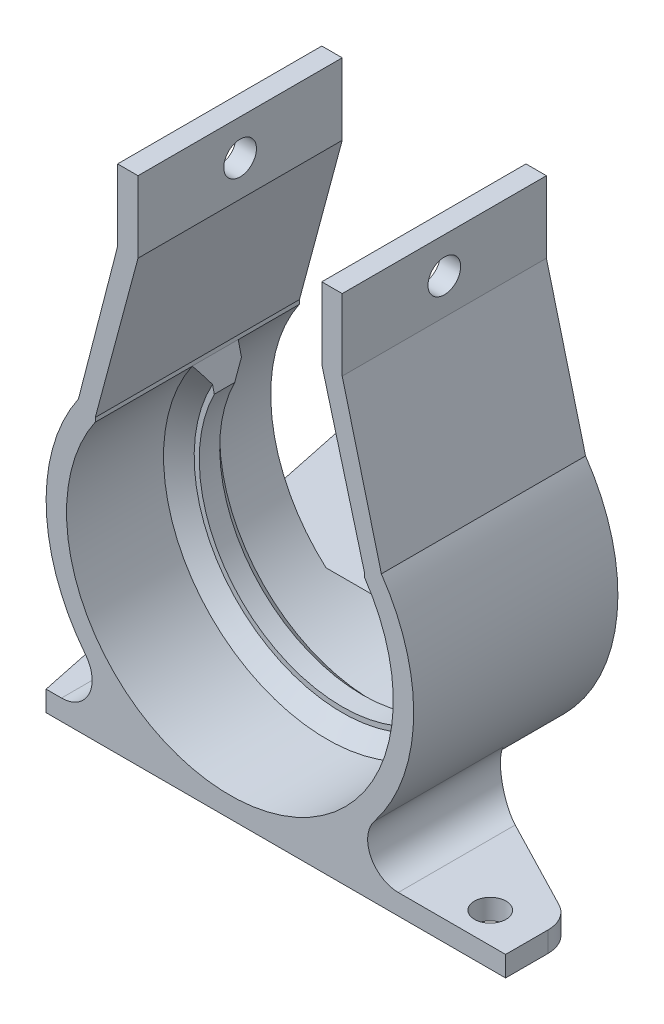
SolidWorks part; units mm, degrees
ref_plane "Front" through (0, 0, 0) normal (0, 0, 1) x (1, 0, 0)
ref_plane "Top" through (0, 0, 0) normal (0, 1, 0) x (1, 0, 0)
ref_plane "Right" through (0, 0, 0) normal (1, 0, 0) x (0, 0, -1)
sketch "Эскиз1" plane through (0, 0, 0) normal (0, 0, 1) x (1, 0, 0)
  circle A0 centre (0, 0) radius 16
  circle A1 centre (0, 0) radius 18
extrude "Бобышка-Вытянуть2" add sketch "Эскиз1" along normal blind 6
sketch "Эскиз2" plane through (0, 0, 6) normal (0, 0, 1) x (1, 0, 0)
  circle A0 centre (0, 0) radius 14
  circle A1 centre (0, 0) radius 18 construction
  circle A2 centre (0, 0) radius 18
extrude "Бобышка-Вытянуть3" add sketch "Эскиз2" along normal blind 3
sketch "Эскиз3" plane through (0, 0, 0) normal (0, 0, -1) x (-1, 0, 0)
  circle A0 centre (0, 0) radius 16 construction
  circle A1 centre (0, 0) radius 18 construction
  circle A2 centre (0, 0) radius 16
  circle A3 centre (0, 0) radius 18
extrude "Бобышка-Вытянуть5" add sketch "Эскиз3" against normal blind 20
sketch "Эскиз4" plane through (0, 0, 20) normal (0, 0, 1) x (1, 0, 0)
  line L0 (0, 0) -> (-14.8349, 10.1945)
  line L1 (14.8349, 10.1945) -> (0, 0)
  circle A0 centre (0, 0) radius 18 construction
  arc A1 (14.8349, 10.1945) -> (-14.8349, 10.1945) centre (0, 0) ccw
extrude "Вырез-Вытянуть1" cut sketch "Эскиз4" against normal blind 20
sketch "Эскиз6" plane through (0, 0, 9) normal (0, 0, 1) x (1, 0, 0)
  line L0 (-13.1865, 9.0617) -> (-12.5248, 6.2553)
  line L1 (12.5248, 6.2553) -> (13.1865, 9.0617)
  line L2 (13.1865, 9.0617) -> (-13.1865, 9.0617)
  line L3 (-12.5248, 6.2553) -> (12.5248, 6.2553)
  arc A0 (-11.5382, 7.929) -> (11.5382, 7.929) centre (0, 0) ccw construction
extrude "Вырез-Вытянуть2" cut sketch "Эскиз6" against normal blind 20
ref_plane "Плоскость1" through (0, 9.05, 0) normal (0, 1, 0) x (1, 0, 0)
sketch "Эскиз8" plane through (0, 9.05, 0) normal (0, 1, 0) x (1, 0, 0)
  line L0 (-13.1865, -20) -> (-13.1865, -9) construction
  line L1 (-13.1865, -9) -> (-13.1865, -6) construction
  line L2 (-13.1865, -6) -> (-13.1865, 0) construction
  line L3 (-13.1865, 0) -> (-14.8349, 0) construction
  line L4 (-14.8349, 0) -> (-14.8349, -20) construction
  line L5 (-14.8349, -20) -> (-13.1865, -20) construction
  line L6 (13.1865, 0) -> (13.1865, -6) construction
  line L7 (13.1865, -6) -> (13.1865, -9) construction
  line L8 (13.1865, -9) -> (13.1865, -20) construction
  line L9 (13.1865, -20) -> (14.8349, -20) construction
  line L10 (14.8349, -20) -> (14.8349, 0) construction
  line L11 (14.8349, 0) -> (13.1865, 0) construction
  line L12 (-13.1865, -20) -> (-13.1865, -9)
  line L13 (-13.1865, -9) -> (-13.1865, -6)
  line L14 (-13.1865, -6) -> (-13.1865, 0)
  line L15 (-13.1865, 0) -> (-14.8349, 0)
  line L16 (-14.8349, 0) -> (-14.8349, -20)
  line L17 (-14.8349, -20) -> (-13.1865, -20)
  line L18 (13.1865, 0) -> (13.1865, -6)
  line L19 (13.1865, -6) -> (13.1865, -9)
  line L20 (13.1865, -9) -> (13.1865, -20)
  line L21 (13.1865, -20) -> (14.8349, -20)
  line L22 (14.8349, -20) -> (14.8349, 0)
  line L23 (14.8349, 0) -> (13.1865, 0)
extrude "Бобышка-Вытянуть8" add sketch "Эскиз8" along normal blind 23
sketch "Эскиз10" plane through (0, 0, 20) normal (0, 0, 1) x (1, 0, 0)
  line L0 (-13.1865, 32.05) -> (13.1865, 32.05) construction
  line L1 (0, 32.05) -> (0, 0) construction
  line L2 (0, 32.05) -> (-11, 32.05) construction
  line L3 (0, 32.05) -> (11, 32.05) construction
  line L4 (-11, 32.05) -> (-11, 25.05)
  line L5 (-11, 32.05) -> (-9, 32.05)
  line L6 (-9, 32.05) -> (-9, 25.05)
  line L7 (-11, 25.05) -> (-14.8349, 10.1945)
  line L8 (-14.8349, 32.05) -> (-14.8349, 10.1945) construction
  line L9 (-9, 25.05) -> (-13.1865, 9.4503)
  line L10 (-13.1865, 32.05) -> (-13.1865, 9.05) construction
  line L11 (-13.1865, 9.4503) -> (-14.8349, 10.1945)
  line L12 (13.1865, 9.4503) -> (14.8349, 10.1945)
  line L13 (11, 25.05) -> (14.8349, 10.1945)
  line L14 (9, 25.05) -> (13.1865, 9.4503)
  line L15 (9, 32.05) -> (9, 25.05)
  line L16 (11, 32.05) -> (9, 32.05)
  line L17 (11, 32.05) -> (11, 25.05)
extrude "Бобышка-Вытянуть9" add sketch "Эскиз10" against normal blind 21
sketch "Эскиз11" plane through (0, 0, 0) normal (0, 0, -1) x (-1, 0, 0)
  line L0 (13.1865, 32.05) -> (13.1865, 16.5797) construction
  line L1 (13.1865, 16.5797) -> (14.8349, 10.1945) construction
  line L2 (14.8349, 10.1945) -> (14.8349, 32.05) construction
  line L3 (14.8349, 32.05) -> (13.1865, 32.05) construction
  line L4 (-14.8349, 32.05) -> (-14.8349, 10.1945) construction
  line L5 (-14.8349, 10.1945) -> (-13.1865, 16.5797) construction
  line L6 (-13.1865, 16.5797) -> (-13.1865, 32.05) construction
  line L7 (-13.1865, 32.05) -> (-14.8349, 32.05) construction
  line L8 (13.1865, 32.05) -> (13.1865, 16.5797)
  line L9 (13.1865, 16.5797) -> (14.8349, 10.1945)
  line L10 (14.8349, 10.1945) -> (14.8349, 32.05)
  line L11 (14.8349, 32.05) -> (13.1865, 32.05)
  line L12 (-14.8349, 32.05) -> (-14.8349, 10.1945)
  line L13 (-14.8349, 10.1945) -> (-13.1865, 16.5797)
  line L14 (-13.1865, 16.5797) -> (-13.1865, 32.05)
  line L15 (-13.1865, 32.05) -> (-14.8349, 32.05)
extrude "Вырез-Вытянуть3" cut sketch "Эскиз11" against normal blind 21
sketch "Эскиз12" plane through (-11, 0, 0) normal (-1, 0, 0) x (0, 0, 1)
  line L0 (0, 10.1945) -> (0, 32.9847)
  line L1 (0, 32.9847) -> (-2.3232, 32.9847)
  line L2 (-2.3232, 32.9847) -> (-2.3232, 10.1945)
  line L3 (0, 10.1945) -> (0, 7.9608)
  line L4 (0, 7.9608) -> (-2.3232, 7.9608)
  line L5 (-2.3232, 7.9608) -> (-2.3232, 10.1945)
extrude "Вырез-Вытянуть4" cut sketch "Эскиз12" against normal blind 29 and the other way blind 19
sketch "Эскиз13" plane through (-11, 0, 0) normal (-1, 0, 0) x (0, 0, 1)
  line L0 (0, 28.55) -> (20, 28.55) construction
  line L1 (0, 32.05) -> (0, 25.05) construction
  line L2 (20, 32.05) -> (20, 25.05) construction
  circle A0 centre (10, 28.55) radius 1.6
extrude "Вырез-Вытянуть5" cut sketch "Эскиз13" against normal blind 29
ref_plane "Плоскость2" through (0, -18, 0) normal (0, -1, 0) x (-1, 0, 0)
sketch "Эскиз15" plane through (0, -18, 0) normal (0, -1, 0) x (-1, 0, 0)
  line L5 (0, -17) -> (0, 18.0294) construction
  line L11 (-22.5, 21) -> (22.5, 21) construction
  line L12 (-22.5, -17) -> (-22.5, 21) construction
  line L13 (0, -17) -> (-22.5, -17) construction
  line L14 (18, -20) -> (26.4151, 20.1801)
  line L15 (0, 0) -> (19.4138, 23.5447)
  line L16 (-25.381, -13.1605) -> (0, 0)
  line L17 (-27, -20) -> (-27, -15.8238)
  line L18 (0, -20) -> (-27, -20)
  line L19 (18, -20) -> (-18, -20)
  arc A4 (-27, -15.8238) -> (-25.381, -13.1605) centre (-24, -15.8238) cw
  arc A5 (19.4138, 23.5447) -> (26.4151, 20.1801) centre (22.5, 21) cw
  circle A6 centre (22.5, 21) radius 1.55
  circle A7 centre (-22.5, -17) radius 1.55
extrude "Бобышка-Вытянуть11" add sketch "Эскиз15" against normal blind 2 contours A5 L15 L16 A4 L17 L18 L19 L14 A6 A7
fillet "Скругление3" radius 3 1 edges at (8.2462, -16, 12.1379)
chamfer "Фаска5" distance 4 angle 45 1 edges at (-8.2462, -16, 0)
chamfer "Фаска6" distance 1.5 angle 45 1 edges at (0, -16, 9)
chamfer "Фаска7" distance 1 angle 45 1 edges at (0, -14, 6)
